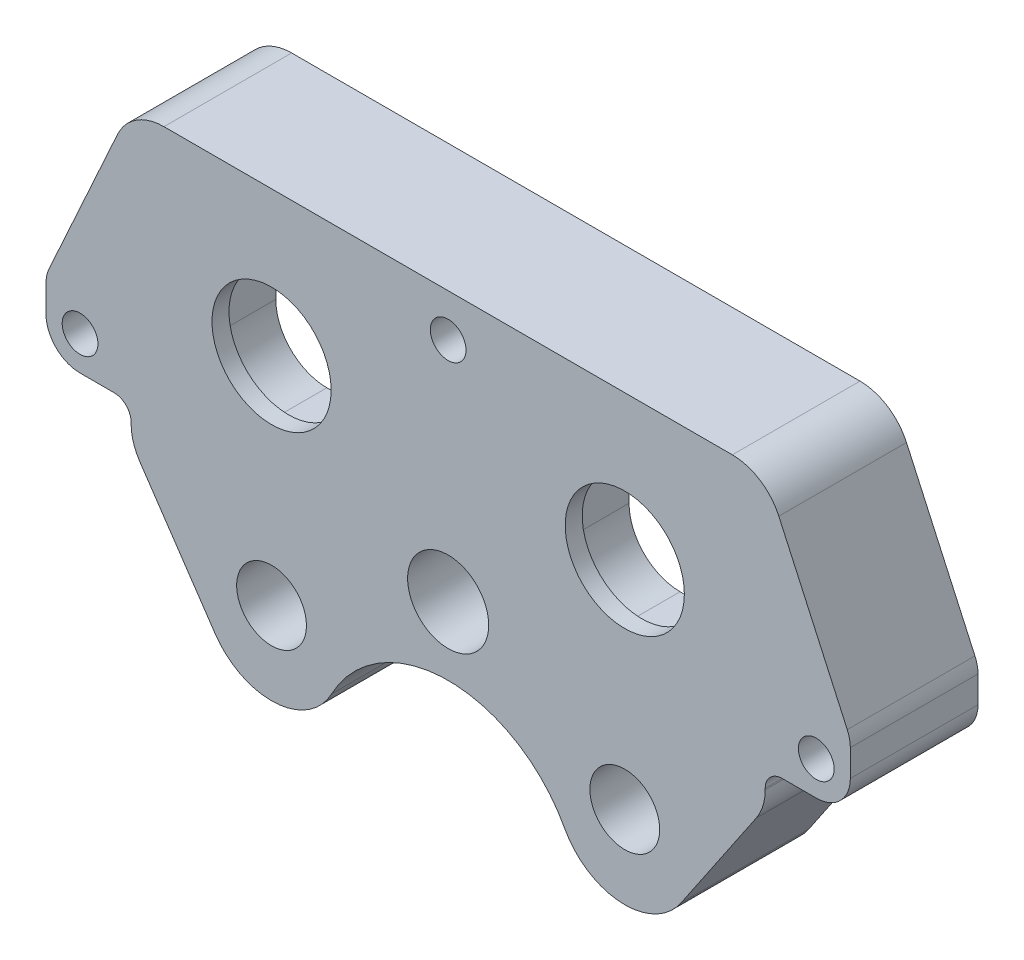
SolidWorks part; units mm, degrees
ref_plane "Front Plane" through (0, 0, 0) normal (0, 0, 1) x (1, 0, 0)
ref_plane "Top Plane" through (0, 0, 0) normal (0, 1, 0) x (1, 0, 0)
ref_plane "Right Plane" through (0, 0, 0) normal (1, 0, 0) x (0, 0, -1)
sketch "Sketch1" plane through (0, 0, 0) normal (0, 0, 1) x (1, 0, 0)
  line L0 (56, 15) -> (27, 15)
  line L1 (14.5, 15) -> (-14.5, 15)
  line L2 (14.5, 15) -> (14.5, -15)
  line L3 (14.5, -15) -> (-14.5, -15)
  line L4 (-14.5, 15) -> (-14.5, -15)
  line L5 (14.5, 15) -> (-14.5, -15) construction
  line L6 (14.5, -15) -> (-14.5, 15) construction
  line L7 (-16.75, -42) -> (16.75, -42)
  line L8 (-16.75, -42) -> (-16.75, 16)
  line L9 (-16.75, 16) -> (16.75, 16)
  line L10 (16.75, -42) -> (16.75, 16)
  line L11 (56, 15) -> (56, -15)
  line L12 (56, -15) -> (27, -15)
  line L13 (27, 15) -> (27, -15)
  line L14 (56, 15) -> (27, -15) construction
  line L15 (56, -15) -> (27, 15) construction
  line L16 (24.75, -42) -> (58.25, -42)
  line L17 (24.75, -42) -> (24.75, 16)
  line L18 (24.75, 16) -> (58.25, 16)
  line L19 (58.25, -42) -> (58.25, 16)
  circle A0 centre (0, 0) radius 19.05 construction
  circle A1 centre (41.5, 0) radius 19.05 construction
  circle A2 centre (20.75, -14.6491) radius 6.35 construction
  circle A3 centre (20.75, -14.6491) radius 41.275 construction
  circle A4 centre (0, 0) radius 7
  circle A5 centre (41.5, 0) radius 7
  circle A6 centre (0, -25.4) radius 4.3
  circle A7 centre (0, -27.1) radius 6.75
  circle A8 centre (41.5, -27.1) radius 6.75
  circle A9 centre (41.5, -25.4) radius 4.3
  point P0 (0, 0)
  point P10 (41.5, 0)
  point P11 (0, -42)
  point P22 (41.5, -42)
  dimension "D6" = 38.1
  dimension "D12" = 38.1
  dimension "D13" = 12.7
  dimension "D15" = 82.55
  dimension "D20" = 14
  dimension "D21" = 14
  dimension "D16" = 8.6
  dimension "D18" = 13.5
  dimension "D1" = 33.5
  dimension "D2" = 29
  dimension "D3" = 30
  dimension "D4" = 16
  dimension "D5" = 58
  dimension "D7" = 33.5
  dimension "D8" = 29
  dimension "D9" = 30
  dimension "D10" = 16
  dimension "D11" = 58
  dimension "D14" = 8
  dimension "D17" = 10.4
  dimension "D19" = 1.7
sketch "Sketch5" plane through (0, 0, 0) normal (0, 0, 1) x (1, 0, 0)
  line L0 (56, 15) -> (27, -15) construction
  line L1 (14.5, 15) -> (-14.5, 15) construction
  line L2 (-16.5, 17) -> (58, 17)
  line L3 (-16.5, 17) -> (-16.5, -35.1)
  line L4 (-16.5, -35.1) -> (58, -35.1)
  line L5 (58, 17) -> (58, -35.1)
  line L6 (-14.5, 15) -> (-14.5, -15) construction
  line L7 (56, 15) -> (56, -15) construction
  line L8 (14.5, -15) -> (-14.5, -15) construction
  line L9 (-16.5, -17) -> (-6.6243, -31.5853)
  line L10 (56, -15) -> (27, -15) construction
  line L11 (58, -17) -> (48.1243, -31.5853)
  line L12 (-26.5, -5) -> (-16.5, 17)
  line L13 (-16.5, -5) -> (-26.5, -5)
  line L14 (-16.5, -5) -> (-16.5, -13)
  line L15 (-16.5, -13) -> (-26.5, -13)
  line L16 (-26.5, -5) -> (-26.5, -13)
  line L17 (58, -5) -> (68, -5)
  line L18 (58, -5) -> (58, -13)
  line L19 (58, -13) -> (68, -13)
  line L20 (68, -5) -> (68, -13)
  line L21 (58, 17) -> (68, -5)
  circle A0 centre (0, 0) radius 7
  circle A1 centre (41.5, 0) radius 7
  circle A2 centre (20.75, -14.6491) radius 4.7625
  circle A3 centre (0, -25.4) radius 4.1
  circle A4 centre (41.5, -25.4) radius 4.1
  circle A5 centre (41.5, -27.1) radius 6.75
  circle A6 centre (0, -27.1) radius 6.75
  circle A7 centre (0, -27.1) radius 8
  circle A8 centre (41.5, -27.1) radius 8
  circle A9 centre (-22.5, -9) radius 2.1
  circle A10 centre (20.75, 12) radius 2.1
  circle A11 centre (64, -9) radius 2.1
  circle A12 centre (20.75, -38.1651) radius 15.5159
  point P32 (-16.5, -17)
  point P39 (58, -17)
  point P58 (20.75, -22.6491)
  dimension "D1" = 9.525
  dimension "D2" = 14
  dimension "D3" = 14
  dimension "D4" = 8.2
  dimension "D5" = 8
  dimension "D6" = 13.5
  dimension "D7" = 13.5
  dimension "D18" = 4.2
  dimension "D22" = 4.2
  dimension "D26" = 4.2
  dimension "D8" = 8
  dimension "D9" = 2
  dimension "D10" = 2
  dimension "D11" = 2
  dimension "D12" = 2
  dimension "D13" = 2
  dimension "D14" = 8
  dimension "D15" = 10
  dimension "D16" = 9
  dimension "D17" = 10
  dimension "D19" = 8
  dimension "D20" = 6
  dimension "D21" = 4
  dimension "D23" = 21
  dimension "D24" = 4
  dimension "D25" = 6
extrude "Boss-Extrude5" add sketch "Sketch5" against normal blind 15 contours A8 A5 | A7 A6 | A6 A3 | A5 A4 | A8 L11 L5 L2 L3 L9 A7 L4 A10 A2 A1 A0 | L13 L16 L15 L3 A9 | L20 L17 L5 L19 A11 | L13 L3 L12 | L21 L5 L17 region at (20.75, -3.08, 0) region at (-19.8333, 2.3333, 0) region at (61.3333, 2.3333, 0) region at (-16.6281, -9, 0) region at (63, -5.1281, 0) region at (-2.2794, -19.668, 0) region at (45.1434, -33.967, 0) region at (34.9409, -27.1, 0) region at (-6.5591, -27.1, 0)
extrude "Cut-Extrude1" cut sketch "Sketch1" along normal blind 13 from surface contours L1 L4 L3 L2 A4 | L0 L13 L12 L11 A5 region at (55.5827, 0, 0) region at (14.0827, 0, 0) starting at face at (20.75, -13.3152, -15)
extrude "Cut-Extrude2" cut sketch "Sketch5<3>" along normal blind 2 from surface contours A5 A4 | A6 A3 region at (34.9409, -27.1, 0) region at (-6.5591, -27.1, 0) starting at face at (0, 0, -15)
sketch "Sketch5<3>" plane through (0, 0, 0) normal (0, 0, 1) x (1, 0, 0) same geometry as "Sketch5"
fillet "Fillet1" radius 6 8 edges at (56, 15, -8.5) (56, -15, -8.5) (27, -15, -8.5) (27, 15, -8.5) (14.5, -15, -8.5) (-14.5, -15, -8.5) (-14.5, 15, -8.5) (14.5, 15, -8.5)
fillet "Fillet2" radius 4 4 edges at (-26.5, -5, -7.5) (-26.5, -13, -7.5) (68, -5, -7.5) (68, -13, -7.5)
fillet "Fillet3" radius 6 4 edges at (-16.5, -17, -7.5) (58, -17, -7.5) (-16.5, 17, -7.5) (58, 17, -7.5)
fillet "Fillet4" radius 2 2 edges at (-16.5, -13, -7.5) (58, -13, -7.5)
extrude "Boss-Extrude6" add sketch "Sketch5<4>" along normal blind 2.3 from surface contours A2 region at (20.75, -14.6491, 0) starting at face at (6.75, -27.1, -15)
sketch "Sketch5<4>" plane through (0, 0, 0) normal (0, 0, 1) x (1, 0, 0) same geometry as "Sketch5"
sketch "Sketch6" plane through (0, 0, 0) normal (0, 0, 1) x (1, 0, 0)
  line L1 (-18.8338, -9) -> (-20.6669, -5.825)
  line L2 (-20.6669, -5.825) -> (-24.3331, -5.825)
  line L3 (-24.3331, -5.825) -> (-26.1662, -9)
  line L4 (-26.1662, -9) -> (-24.3331, -12.175)
  line L5 (-24.3331, -12.175) -> (-20.6669, -12.175)
  line L6 (-20.6669, -12.175) -> (-18.8338, -9)
  line L7 (24.287, 11.0352) -> (23.354, 14.5807)
  line L8 (23.354, 14.5807) -> (19.817, 15.5455)
  line L9 (19.817, 15.5455) -> (17.213, 12.9648)
  line L10 (17.213, 12.9648) -> (18.146, 9.4193)
  line L11 (18.146, 9.4193) -> (21.683, 8.4545)
  line L12 (21.683, 8.4545) -> (24.287, 11.0352)
  line L13 (60.3338, -9) -> (62.1669, -12.175)
  line L14 (62.1669, -12.175) -> (65.8331, -12.175)
  line L15 (65.8331, -12.175) -> (67.6662, -9)
  line L16 (67.6662, -9) -> (65.8331, -5.825)
  line L17 (65.8331, -5.825) -> (62.1669, -5.825)
  line L18 (62.1669, -5.825) -> (60.3338, -9)
  circle A0 centre (-22.5, -9) radius 3.175 construction
  circle A1 centre (20.75, 12) radius 3.175 construction
  circle A2 centre (64, -9) radius 3.175 construction
  dimension "D1" = 6.35
  dimension "D2" = 6.35
  dimension "D3" = 6.35
